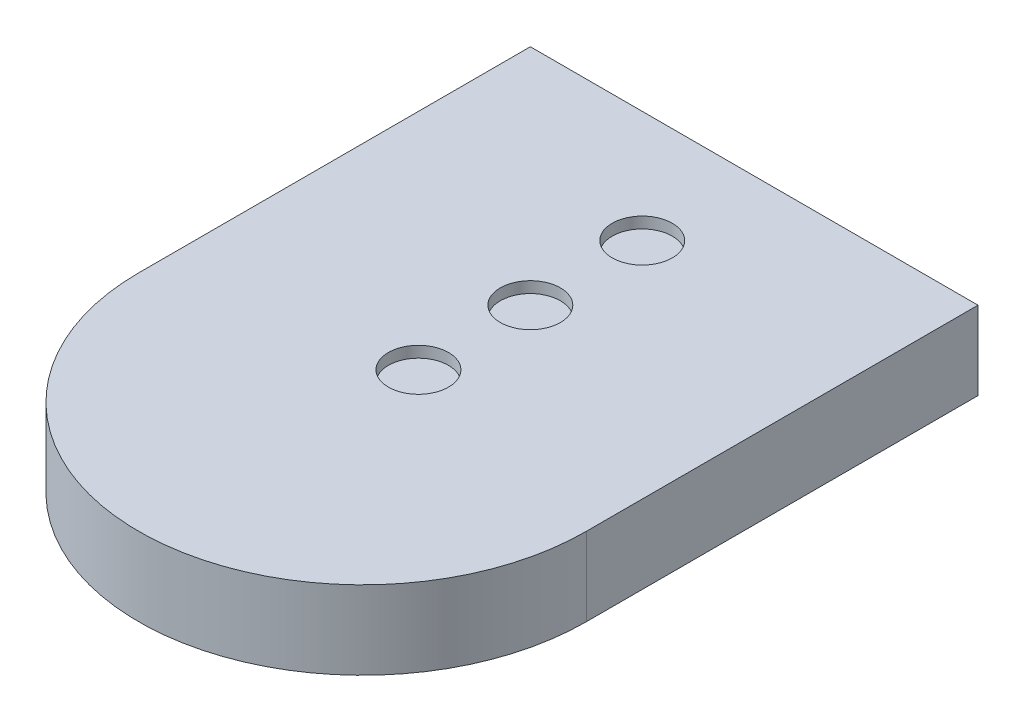
SolidWorks part; units mm, degrees
material "Rubber"
ref_plane "Front Plane" through (0, 0, 0) normal (0, 0, 1) x (1, 0, 0)
ref_plane "Top Plane" through (0, 0, 0) normal (0, 1, 0) x (1, 0, 0)
ref_plane "Right Plane" through (0, 0, 0) normal (1, 0, 0) x (0, 0, -1)
sketch "Sketch1" plane through (0, 0, 0) normal (0, 0, 1) x (1, 0, 0)
  line L0 (0, 0) -> (0, -7)
  line L4 (0, 0) -> (40, 0)
  line L5 (0, -7) -> (40, -7)
  line L6 (40, -7) -> (40, 0)
  dimension "D1" = 40
  dimension "D2" = 7
extrude "Boss-Extrude1" add sketch "Sketch1" along normal blind 55
sketch "Sketch2" plane through (0, 0, 0) normal (0, 1, 0) x (1, 0, 0)
  line L0 (40, 0) -> (0, 0) construction
  line L1 (40, -55) -> (40, 0) construction
  circle A0 centre (20, -10) radius 2.6845
  circle A1 centre (20, -20) radius 2.6845
  circle A2 centre (20, -30) radius 2.6845
  dimension "D1" = 10
  dimension "D2" = 20
  dimension "D3" = 3
extrude "Cut-Extrude1" cut sketch "Sketch2" against normal blind 7
fillet "Fillet1" 2 edges at (40, -3.5, 55) (0, -3.5, 55) type full round first side face at (40, -3.5, 27.5) second side face at (0, -3.5, 27.5) middle face at (20, -3.5, 55)
sketch "Sketch4" plane through (0, 0, 0) normal (0, 0, -1) x (-1, 0, 0)
  line L0 (-40, 0) -> (0, 0) construction
  line L1 (-30, -1) -> (-10, -1)
  line L2 (-30, -1) -> (-30, -6)
  line L3 (-30, -6) -> (-10, -6)
  line L4 (-10, -1) -> (-10, -6)
  line L5 (-30, -1) -> (-10, -6) construction
  line L6 (-30, -6) -> (-10, -1) construction
  line L8 (0, 0) -> (0, -7) construction
  point P0 (-20, -3.5)
  dimension "D1" = 1
  dimension "D2" = 5
  dimension "D3" = 20
  dimension "D4" = 10
extrude "Cut-Extrude2" cut sketch "Sketch4" against normal blind 40
